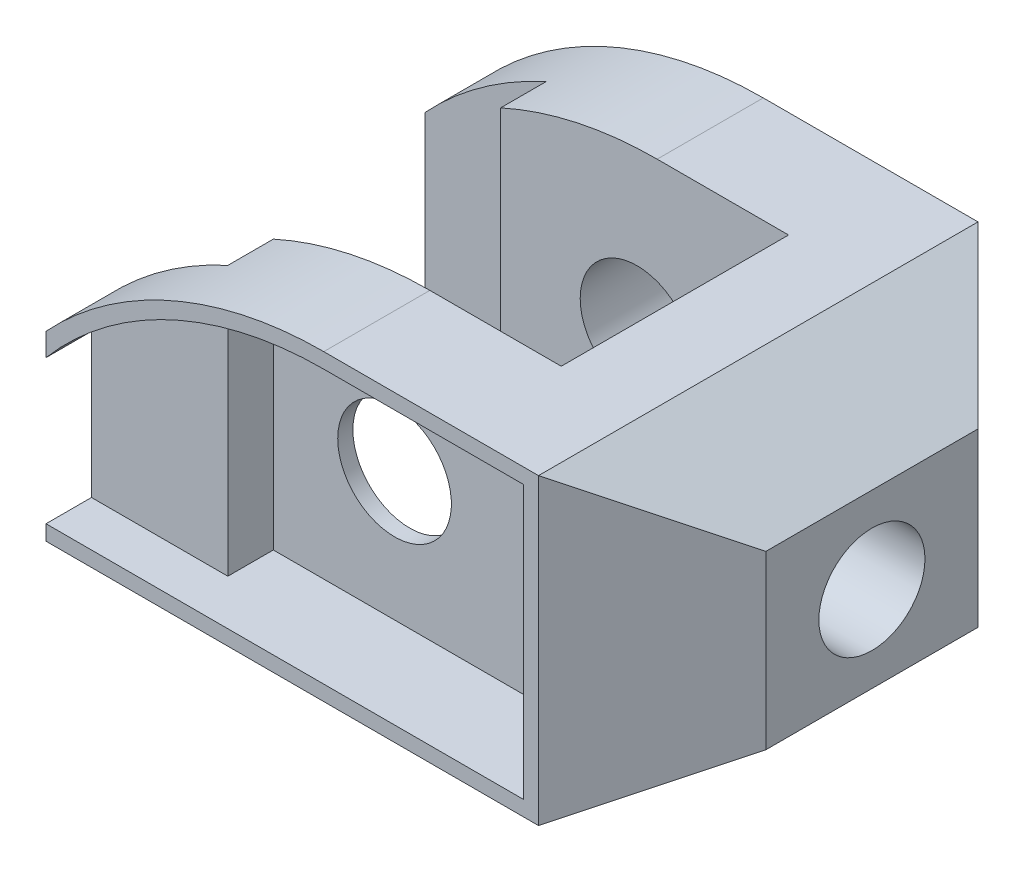
SolidWorks part; units mm, degrees
material "1060 Alloy"
ref_plane "Front Plane" through (0, 0, 0) normal (0, 0, 1) x (1, 0, 0)
ref_plane "Top Plane" through (0, 0, 0) normal (0, 1, 0) x (1, 0, 0)
ref_plane "Right Plane" through (0, 0, 0) normal (1, 0, 0) x (0, 0, -1)
sketch "Sketch1" plane through (0, 0, 0) normal (0, 0, 1) x (1, 0, 0)
  line L0 (0, 0) -> (65, 0)
  line L1 (0, 0) -> (0, 24)
  line L2 (65, 0) -> (80, 8.6603)
  line L3 (80, 8.6603) -> (80, 31.3397)
  line L4 (80, 31.3397) -> (65, 40)
  line L5 (65, 40) -> (36.6606, 40)
  arc A0 (36.6606, 40) -> (0, 24) centre (36.6606, -10) ccw
  circle A1 centre (34, 19) radius 7.5
  dimension "D8" = 50
  dimension "D9" = 31
  dimension "D11" = 15
  dimension "D1" = 65
  dimension "D2" = 24
  dimension "D3" = 15
  dimension "D4" = 15
  dimension "D5" = 40
  dimension "D6" = 30
  dimension "D7" = 30
  dimension "D10" = 19
extrude "Boss-Extrude1" add sketch "Sketch1" along normal mid plane 58
sketch "Sketch2" plane through (0, 0, 0) normal (0, 1, 0) x (1, 0, 0)
  line L0 (0, -29) -> (0, 29) construction
  line L1 (0, 21) -> (16, 21)
  line L2 (0, 21) -> (0, -21)
  line L3 (0, -21) -> (16, -21)
  line L4 (16, 21) -> (16, 15)
  line L5 (36.6606, 29) -> (0, 29) construction
  line L6 (16, 15) -> (54, 15)
  line L8 (16, -15) -> (54, -15)
  line L9 (54, 15) -> (54, -15)
  line L10 (0, -29) -> (36.6606, -29) construction
  line L11 (65, -29) -> (65, 29) construction
  line L12 (16, -15) -> (16, -21)
  dimension "D1" = 8
  dimension "D2" = 8
  dimension "D3" = 6
  dimension "D4" = 6
  dimension "D5" = 11
  dimension "D6" = 16
extrude "Cut-Extrude1" cut sketch "Sketch2" along normal blind 72 and the other way through all
sketch "Sketch3" plane through (0, 0, 0) normal (0, 1, 0) x (1, 0, 0)
  line L0 (80, 29) -> (65, 29)
  line L1 (65, 29) -> (80, 14)
  line L2 (80, -29) -> (80, 29) construction
  line L3 (80, 14) -> (80, 29)
  line L4 (65, -29) -> (80, -14)
  line L5 (80, -14) -> (80, -29)
  line L6 (80, -29) -> (65, -29) construction
  line L7 (80, -29) -> (65, -29)
  dimension "D1" = 45
  dimension "D2" = 45
extrude "Cut-Extrude2" cut sketch "Sketch3" along normal blind 72
sketch "Sketch4" plane through (80, 0, 0) normal (1, 0, 0) x (0, 0, -1)
  line L0 (-29, 0) -> (29, 0) construction
  line L1 (29, 40) -> (29, 0) construction
  circle A0 centre (0, 20) radius 7
  dimension "D1" = 14
  dimension "D2" = 20
  dimension "D3" = 29
extrude "Cut-Extrude3" cut sketch "Sketch4" against normal through all both and the other way through all
sketch "Sketch5" plane through (0, 0, 29) normal (0, 0, 1) x (1, 0, 0)
  line L4 (0, 0) -> (65, 0)
  line L5 (65, 0) -> (65, 40)
  line L6 (65, 40) -> (36.6606, 40)
  line L7 (0, 24) -> (0, 0)
  line L8 (0, 0) -> (65, 0)
  line L9 (65, 0) -> (65, 40)
  line L10 (65, 40) -> (36.6606, 40)
  line L11 (0, 24) -> (0, 0)
  line L12 (16, 0) -> (16, 35.5317) construction
  line L13 (16, 0) -> (16, 35.5317) construction
  line L14 (18, 34.2242) -> (18, 2)
  line L16 (2, 2) -> (63, 2)
  line L17 (63, 2) -> (63, 38)
  line L18 (63, 38) -> (36.6606, 38)
  line L19 (2, 23.2061) -> (2, 2)
  line L20 (0, 2) -> (63, 2)
  line L21 (63, 2) -> (63, 38)
  line L22 (63, 38) -> (36.6606, 38)
  arc A1 (36.6606, 40) -> (0, 24) centre (36.6606, -10) ccw
  arc A2 (36.6606, 40) -> (0, 24) centre (36.6606, -10) ccw
  arc A4 (36.6606, 38) -> (2, 23.2061) centre (36.6606, -10) ccw
  arc A5 (36.6606, 38) -> (0, 20.9839) centre (36.6606, -10) ccw
  circle M13 centre (34, 19) radius 7.5
  dimension "D3" = 2
  dimension "D1" = 0
  dimension "D2" = 2
extrude "Cut-Extrude5" cut sketch "Sketch5" against normal blind 12 contours L22 A5 L14 L20 L21 M13 region at (41.5996, 19.8499, 29)
extrude "Cut-Extrude6" cut sketch "Sketch5<4>" against normal blind 6 contours L20 L13 A5 L11 | L13 L20 L14 A5 region at (1.0184, 12.0693, 29) region at (9.4343, 15.6127, 29) region at (17.0047, 17.8932, 29)
sketch "Sketch5<4>" plane through (0, 0, 29) normal (0, 0, 1) x (1, 0, 0) same geometry as "Sketch5"
equation "\"a\"= 58"
equation "\"b\"= 40"
equation "\"c\"= 65"
